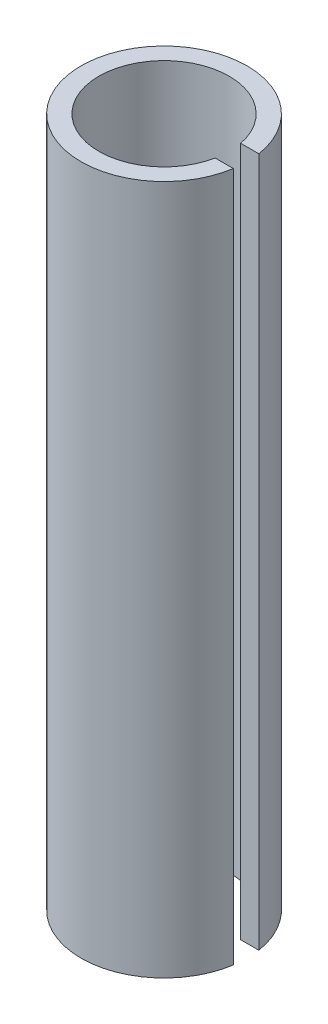
SolidWorks part; units mm, degrees
ref_plane "Front Plane" through (0, 0, 0) normal (0, 0, 1) x (1, 0, 0)
ref_plane "Top Plane" through (0, 0, 0) normal (0, 1, 0) x (1, 0, 0)
ref_plane "Right Plane" through (0, 0, 0) normal (1, 0, 0) x (0, 0, -1)
sketch "Sketch1" plane through (0, 0, 0) normal (0, 1, 0) x (1, 0, 0)
  line L0 (2.5005, 0.5) -> (3.2113, 0.5)
  line L1 (2.5005, -0.5) -> (3.2113, -0.5)
  line L2 (0, 0) -> (3.25, 0) construction
  circle A0 centre (0, 0) radius 3.25
  circle A1 centre (0, 0) radius 2.55
  dimension "D1" = 5.1
  dimension "D2" = 6.5
  dimension "D3" = 1
  dimension "D4" = 0.5
extrude "Boss-Extrude1" add sketch "Sketch1" along normal blind 27 contours A1 L0 A0 L1 region at (-2.6417, 0, 0)
